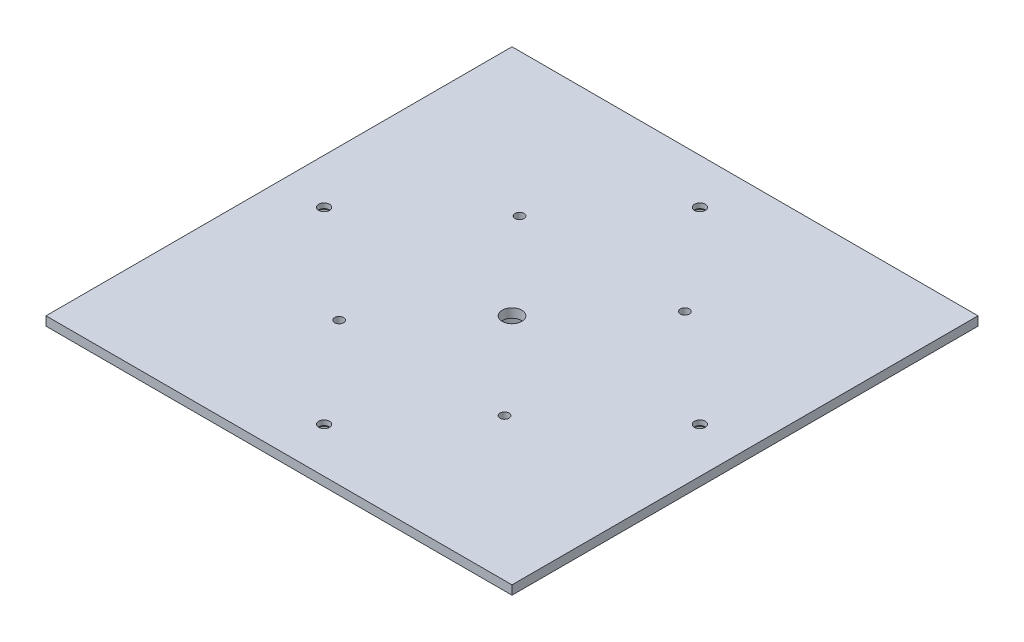
SolidWorks part; units mm, degrees
ref_plane "Front Plane" through (0, 0, 0) normal (0, 0, 1) x (1, 0, 0)
ref_plane "Top Plane" through (0, 0, 0) normal (0, 1, 0) x (1, 0, 0)
ref_plane "Right Plane" through (0, 0, 0) normal (1, 0, 0) x (0, 0, -1)
sketch "Sketch10" plane through (0, 0, 0) normal (0, -1, 0) x (1, 0, 0)
  line L0 (-67.8708, 79.6477) -> (-67.8708, 7.5) construction
  line L2 (-152.8708, -77.5) -> (-152.8708, 77.5)
  line L3 (-152.8708, 77.5) -> (2.1292, 77.5)
  line L4 (2.1292, -77.5) -> (2.1292, 77.5)
  line L5 (0, -55) -> (0, 55) construction
  line L7 (-67.8708, 7.5) -> (4.2768, 7.5) construction
  line L8 (-152.8708, -77.5) -> (2.1292, -77.5)
  line L9 (-82.8708, -79.6477) -> (-82.8708, -7.5) construction
  line L11 (55, 0) -> (-55, 0) construction
  point P22 (-75.3708, 0)
  dimension "D3" = 2.1292
  dimension "D1" = 155
  dimension "D2" = 155
  dimension "D4" = 77.5
extrude "Boss-Extrude3" add sketch "Sketch10" along normal blind 3
sketch "Sketch11" plane through (0, -3, 0) normal (0, -1, 0) x (1, 0, 0)
  line L0 (-152.8708, 77.5) -> (-135.2608, 77.5) construction
  line L1 (2.1292, 77.5) -> (-152.8708, 77.5) construction
  line L2 (-135.2608, 77.5) -> (-135.2608, 59.89) construction
  line L3 (-75.3708, -33.4232) -> (-75.3708, 33.4232) construction
  line L4 (1.65, 0) -> (-1.65, 0) construction
  line L5 (-152.8708, 77.5) -> (-152.8708, -77.5) construction
  circle A1 centre (-135.2608, 59.89) radius 2.3
  circle A2 centre (-15.4808, 59.89) radius 2.3
  circle A3 centre (-15.4808, -59.89) radius 2.3
  circle A4 centre (-135.2608, -59.89) radius 2.3
  circle A5 centre (-75.3708, 0) radius 17.5
  circle A6 centre (-75.3708, 0) radius 12.59
  point P13 (-75.3708, 0)
  dimension "D1" = 77.5
  dimension "D4" = 4.6
  dimension "D7" = 25.18
  dimension "D6" = 35
  dimension "D2" = 17.61
  dimension "D3" = 17.61
  dimension "D5" = 77.5
extrude "Boss-Extrude4" add sketch "Sketch11" along normal blind 8.4 contours A5 region at (-92.3759, -3, 0)
extrude "Boss-Extrude6" add sketch "Sketch11<4>" along normal blind 4 contours A1 | A2 | A4 | A3 region at (-135.2608, -3, 59.89) region at (-15.4808, -3, 59.89) region at (-15.4808, -3, -59.89) region at (-135.2608, -3, -59.89)
sketch "Sketch11<4>" plane through (0, -3, 0) normal (0, -1, 0) x (1, 0, 0) same geometry as "Sketch11"
sketch "Sketch12" plane through (0, 0, 0) normal (0, 0, 1) x (1, 0, 0)
  line L0 (-75.3708, -11.4) -> (-75.3708, -6.9) construction
  line L1 (-92.8708, -11.4) -> (-57.8708, -11.4) construction
  circle A0 centre (-75.3708, -6.9) radius 2.55
  dimension "D2" = 5.1
  dimension "D1" = 4.5
extrude "Cut-Extrude1" cut sketch "Sketch12" against normal blind 37
sketch "Sketch14" plane through (0, 0, 0) normal (1, 0, 0) x (0, 0, -1)
  line L0 (0, -11.4) -> (0, -6.9) construction
  line L1 (-17.5, -11.4) -> (17.5, -11.4) construction
  line L2 (0, 6.27) -> (0, -6.27) construction
  circle A0 centre (0, -6.9) radius 2.55
  dimension "D2" = 5.1
  dimension "D1" = 4.5
extrude "Cut-Extrude2" cut sketch "Sketch14" against normal blind 75
sketch "Sketch15" plane through (0, 0, 0) normal (0, 1, 0) x (1, 0, 0)
  line L0 (-6.27, 0) -> (6.27, 0) construction
  line L1 (-152.8708, -77.5) -> (-152.8708, 77.5) construction
  line L2 (-75.3708, -17.0682) -> (-75.3708, 17.0682) construction
  circle A0 centre (-102.8708, 30) radius 1.5
  circle A1 centre (-47.8708, 30) radius 1.5
  circle A2 centre (-47.8708, -30) radius 1.5
  circle A3 centre (-102.8708, -30) radius 1.5
  circle A4 centre (-75.3708, 0) radius 3.25
  point P9 (-75.3708, 0)
  point P14 (-75.3708, 0)
  dimension "D1" = 3
  dimension "D4" = 77.5
  dimension "D5" = 6.5
  dimension "D2" = 30
  dimension "D3" = 50
extrude "Cut-Extrude3" cut sketch "Sketch15" against normal blind 95
sketch "Sketch16" plane through (0, -3, 0) normal (0, -1, 0) x (1, 0, 0)
  line L0 (-75.3708, 62.5) -> (-75.3708, -62.5) construction
  line L1 (-137.8708, 0) -> (-12.8708, 0) construction
  circle A0 centre (-75.3708, 0) radius 3.25 construction
  circle A1 centre (-75.3708, 0) radius 3.25 construction
  point P6 (-75.3708, 0)
  point P10 (-75.3708, 0)
  dimension "D1" = 125
hole_wizard "CSK for M3 Flat Head Machine Screw1" positions "Sketch20" profile "Sketch18" countersink size "M3" standard "ANSI Metric" end condition through all
sketch "Sketch20" plane through (0, -3, 0) normal (0, -1, 0) x (-1, 0, 0)
  point P0 (75.3708, 62.5)
  point P3 (12.8708, 0)
  point P6 (75.3708, -62.5)
  point P9 (137.8708, 0)
sketch "Sketch18" plane through (-75.3708, -3, -62.5) normal (1, 0, 0) x (0, 0, -1)
  line L0 (0, 0) -> (0, 3)
  line L1 (0, 3) -> (1.8, 3)
  line L2 (1.8, 3) -> (1.8, 1.35)
  line L3 (1.8, 1.35) -> (3.15, 0)
  line L5 (3.15, 0) -> (0, 0)
  line L6 (-1.8, 1.35) -> (-3.15, 0) construction
  line L11 (0, -6.35) -> (0, 107.95) construction
  dimension "Thru Hole Dia." = 3.6
  dimension "Thru Hole Depth" = 3
  dimension "Near C'Sink Dia." = 6.3
  dimension "Near C'Sink Angle" = 90
